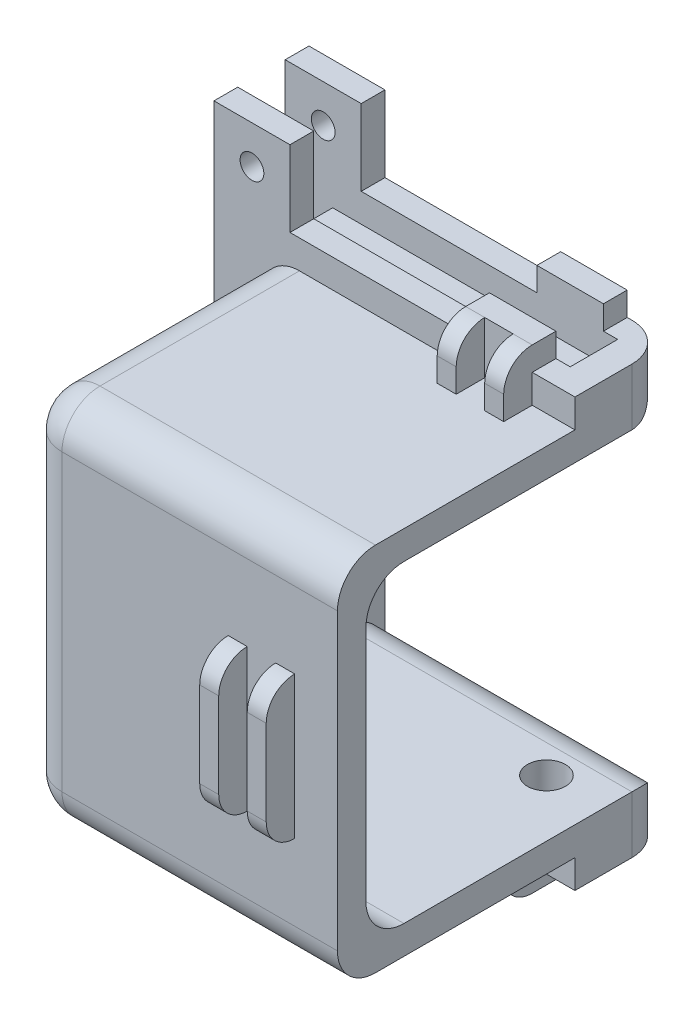
SolidWorks part; units mm, degrees
material "PVC rigido"
ref_plane "Piano frontale" through (0, 0, 0) normal (0, 0, 1) x (1, 0, 0)
ref_plane "Piano superiore" through (0, 0, 0) normal (0, 1, 0) x (1, 0, 0)
ref_plane "Piano destro" through (0, 0, 0) normal (1, 0, 0) x (0, 0, -1)
sketch "Schizzo1" plane through (0, 0, 0) normal (0, 0, 1) x (1, 0, 0)
  line L0 (8, 0) -> (0, 0) construction
  line L1 (0, -22.5) -> (38, -22.5)
  line L2 (0, -22.5) -> (0, 22.5)
  line L3 (0, 22.5) -> (38, 22.5)
  line L4 (38, 22.5) -> (38, 16.5)
  line L5 (8, -16.5) -> (38, -16.5)
  line L6 (8, -16.5) -> (8, 16.5)
  line L7 (8, 16.5) -> (38, 16.5)
  line L8 (38, -16.5) -> (38, -22.5)
  line L10 (8, 16.5) -> (8, 19.5) construction
  line L11 (5, 19.5) -> (35, 19.5) construction
  dimension "D1" = 6
  dimension "D2" = 38
  dimension "D3" = 3
  dimension "D4" = 8
extrude "Estrusione-Estrusione1" add sketch "Schizzo1" along normal blind 10 contours L2 L3 L4 L7 L6 L5 L8 L1
sketch "Schizzo6" plane through (0, 0, 10) normal (0, 0, 1) x (1, 0, 0)
  line L0 (8, -16.5) -> (8, 16.5) construction
  line L1 (0, -22.5) -> (8, -22.5)
  line L2 (0, -22.5) -> (0, -30.5)
  line L3 (0, -30.5) -> (8, -30.5)
  line L4 (8, -22.5) -> (8, -30.5)
  line L5 (0, 22.5) -> (8, 22.5)
  line L6 (0, 22.5) -> (0, 30.5)
  line L7 (0, 30.5) -> (8, 30.5)
  line L8 (8, 22.5) -> (8, 30.5)
  line L10 (33.5, -22.5) -> (26.5, -22.5)
  line L11 (33.5, -22.5) -> (33.5, -25)
  line L12 (33.5, -25) -> (26.5, -25)
  line L13 (26.5, -22.5) -> (26.5, -25)
  line L14 (33.5, 22.5) -> (26.5, 22.5)
  line L15 (33.5, 22.5) -> (33.5, 25)
  line L16 (33.5, 25) -> (26.5, 25)
  line L17 (26.5, 22.5) -> (26.5, 25)
  line L18 (0, -22.5) -> (38, -22.5) construction
  line L19 (0, 22.5) -> (38, 22.5) construction
  line L20 (30, -25) -> (30, -22.5) construction
  line L21 (38, -16.5) -> (38, -22.5) construction
  dimension "D1" = 7
  dimension "D2" = 8
  dimension "D3" = 50
extrude "Estrusione-Estrusione4" add sketch "Schizzo6" against normal up to surface (10 mm away) up to face at (21, 0, 0)
sketch "Schizzo2" plane through (38, 0, 0) normal (1, 0, 0) x (0, 0, -1)
  line L0 (-10, -22.5) -> (0, -22.5) construction
  line L1 (-7.5, -22.5) -> (-7.5, -41.8171)
  line L2 (-7.5, -22.5) -> (-7.5, -19.5)
  line L3 (-7.5, -19.5) -> (-2.5, -19.5)
  line L4 (-2.5, -22.5) -> (-2.5, -19.5)
  line L5 (-5, -19.5) -> (-5, -16.5) construction
  line L6 (-10, -16.5) -> (0, -16.5) construction
  line L7 (-7.5, -41.8171) -> (-2.5, -41.8171)
  line L8 (-2.5, -41.8171) -> (-2.5, -22.5)
  dimension "D1" = 3
  dimension "D2" = 5
extrude "Taglio-Estrusione1" cut sketch "Schizzo2" against normal through all
sketch "Schizzo4" plane through (0, -19.5, 0) normal (0, -1, 0) x (-1, 0, 0)
  line L0 (0, -7.5) -> (-38, -7.5) construction
  line L1 (-38, -2.5) -> (-35, -2.5)
  line L2 (-38, -2.5) -> (-38, -7.5)
  line L3 (-38, -7.5) -> (-35, -7.5)
  line L4 (-35, -2.5) -> (-35, -7.5)
  line L5 (-35, -7.5) -> (-35, -2.5) construction
extrude "Estrusione-Estrusione2" add sketch "Schizzo4" along normal up to surface (3 mm away) up to face at (35.1875, -22.5, 1.25)
mirror "Specchia1" about plane through (0, 0, 0) normal (0, 1, 0) of "Taglio-Estrusione1"
sketch "Schizzo5" plane through (0, 19.5, 0) normal (0, 1, 0) x (1, 0, 0)
  line L0 (0, -2.5) -> (38, -2.5) construction
  line L1 (38, -2.5) -> (35, -2.5)
  line L2 (38, -2.5) -> (38, -7.5)
  line L3 (38, -7.5) -> (35, -7.5)
  line L4 (35, -2.5) -> (35, -7.5)
  line L5 (38, -2.5) -> (38, -7.5) construction
  line L6 (0, -7.5) -> (38, -7.5) construction
  line L7 (35, -2.5) -> (35, -7.5) construction
extrude "Estrusione-Estrusione3" add sketch "Schizzo5" along normal up to surface (3 mm away) up to face at (35.1875, 22.5, 8.75)
sketch "Schizzo3" plane through (0, -19.5, 0) normal (0, -1, 0) x (1, 0, 0)
  line L0 (0, 7.5) -> (35, 7.5) construction
  line L1 (0, 2.5) -> (5, 2.5)
  line L2 (0, 2.5) -> (0, 7.5)
  line L3 (0, 7.5) -> (5, 7.5)
  line L4 (5, 2.5) -> (5, 7.5)
  dimension "D1" = 5
extrude "Taglio-Estrusione2" cut sketch "Schizzo3" against normal through all
hole_wizard "Foro filettato M3x0.5-1" positions "Schizzo8" profile "Schizzo7" tap size "M3x0.5" standard "Ansi Metric" end condition through all
sketch "Schizzo8" plane through (0, 0, 10) normal (0, 0, 1) x (1, 0, 0)
  line L0 (8, -26.5) -> (4, -26.5) construction
  line L1 (8, -30.5) -> (8, -22.5) construction
  line L2 (4, -26.5) -> (4, -30.5) construction
  line L3 (0, -30.5) -> (8, -30.5) construction
  line L5 (8, 26.5) -> (4, 26.5) construction
  line L6 (8, 22.5) -> (8, 30.5) construction
  line L7 (4, 26.5) -> (4, 30.5) construction
  line L8 (8, 30.5) -> (0, 30.5) construction
  point P0 (4, -26.5)
  point P2 (4, 26.5)
sketch "Schizzo7" plane through (4, -26.5, 10) normal (1, 0, 0) x (0, -1, 0)
  line L0 (0, 0) -> (0, 10)
  line L1 (0, 10) -> (1.25, 10)
  line L2 (1.25, 10) -> (1.25, 0)
  line L5 (1.25, 0) -> (0, 0)
  line L11 (0, -6.35) -> (0, 107.95) construction
  dimension "Thru Tap Drill Dia." = 2.5
  dimension "Thru Tap Drill Depth" = 10
cosmetic thread "Filettatura del foro1" parameters "D2"=3
cosmetic thread "Filettatura del foro2" parameters "D2"=3
sketch "Schizzo9" plane through (0, 0, 10) normal (0, 0, 1) x (1, 0, 0)
  line L0 (38, 22.5) -> (38, 16.5) construction
  line L1 (5, -19.5) -> (38, -19.5)
  line L2 (5, -19.5) -> (5, 19.5)
  line L3 (5, 19.5) -> (38, 19.5)
  line L4 (38, -19.5) -> (38, -16.5)
  line L5 (38, -16.5) -> (8, -16.5)
  line L6 (8, -16.5) -> (8, 16.5)
  line L7 (8, -16.5) -> (8, 16.5) construction
  line L8 (8, 16.5) -> (38, 16.5)
  line L9 (38, 16.5) -> (38, 19.5)
  line L10 (38, -16.5) -> (38, -22.5) construction
  line L11 (5, 0) -> (8, 0) construction
extrude "Estrusione-Estrusione5" add sketch "Schizzo9" along normal blind 25
sketch "Schizzo10" plane through (8, 0, 0) normal (1, 0, 0) x (0, 0, -1)
  line L0 (-35, 16.5) -> (0, 16.5) construction
  line L1 (-35, -16.5) -> (-32, -16.5)
  line L2 (-35, -16.5) -> (-35, 16.5)
  line L3 (-35, 16.5) -> (-32, 16.5)
  line L4 (-32, -16.5) -> (-32, 16.5)
  line L5 (-35, -19.5) -> (-35, -16.5) construction
extrude "Estrusione-Estrusione6" add sketch "Schizzo10" along normal up to surface (30 mm away) up to face at (38, -19.25, 17.0833)
sketch "Schizzo14" plane through (0, -19.5, 0) normal (0, -1, 0) x (1, 0, 0)
  line L0 (32, 7) -> (38, 7) construction
  line L1 (38, 35) -> (38, 10) construction
  line L2 (32, 7) -> (32, 35) construction
  line L5 (5, 35) -> (38, 35) construction
  circle A0 centre (32, 7) radius 2
  dimension "D1" = 6
  dimension "D3" = 4
  dimension "D2" = 28
extrude "Taglio-Estrusione3" cut sketch "Schizzo14" against normal up to surface (39 mm away) up to face at (25.625, 19.5, 25.625)
sketch "Schizzo11" plane through (0, 0, 35) normal (0, 0, 1) x (1, 0, 0)
  line L0 (38, 0) -> (33.5, 0) construction
  line L1 (33.5, -7.5) -> (31.5, -7.5)
  line L2 (33.5, -7.5) -> (33.5, 7.5)
  line L3 (33.5, 7.5) -> (31.5, 7.5)
  line L4 (31.5, -7.5) -> (31.5, 7.5)
  line L5 (26.5, -7.5) -> (28.5, -7.5)
  line L6 (26.5, -7.5) -> (26.5, 7.5)
  line L7 (26.5, 7.5) -> (28.5, 7.5)
  line L8 (28.5, -7.5) -> (28.5, 7.5)
  line L9 (38, -19.5) -> (38, 19.5) construction
  line L10 (33.5, 0) -> (31.5, 0) construction
  line L11 (31.5, 0) -> (28.5, 0) construction
  line L12 (28.5, 0) -> (26.5, 0) construction
  dimension "D1" = 2
  dimension "D2" = 15
  dimension "D3" = 3
  dimension "D4" = 11.5
extrude "Estrusione-Estrusione7" add sketch "Schizzo11" along normal blind 3
sketch "Schizzo12" plane through (0, 0, 10) normal (0, 0, 1) x (1, 0, 0)
  line L0 (5, -19.5) -> (38, -19.5) construction
  line L1 (33.5, -25) -> (31.5, -25)
  line L2 (33.5, -25) -> (33.5, -19.5)
  line L3 (33.5, -19.5) -> (31.5, -19.5)
  line L4 (31.5, -25) -> (31.5, -19.5)
  line L5 (28.5, -7.5) -> (28.5, 7.5) construction
  line L6 (26.5, -25) -> (28.5, -25)
  line L7 (26.5, -25) -> (26.5, -19.5)
  line L8 (26.5, -19.5) -> (28.5, -19.5)
  line L9 (28.5, -25) -> (28.5, -19.5)
  line L10 (31.5, 7.5) -> (31.5, -7.5) construction
extrude "Estrusione-Estrusione8" add sketch "Schizzo12" along normal blind 3
mirror "Specchia2" about plane through (0, 0, 0) normal (0, 1, 0) of "Estrusione-Estrusione8"
fillet "Raccordo1" radius 4 11 edges at (21.5, -19.5, 35) (21.5, 19.5, 35) (5, 0, 35) (5, 19.5, 22.5) (5, -19.5, 22.5) (38, 19.5, 0) (38, -19.5, 0) (23, -16.5, 0) (23, 16.5, 0) (23, 16.5, 32) (23, -16.5, 32)
fillet "Raccordo2" radius 3 8 edges at (27.5, 25, 13) (32.5, 25, 13) (32.5, 7.5, 38) (27.5, 7.5, 38) (27.5, -7.5, 38) (32.5, -7.5, 38) (27.5, -25, 13) (32.5, -25, 13)
